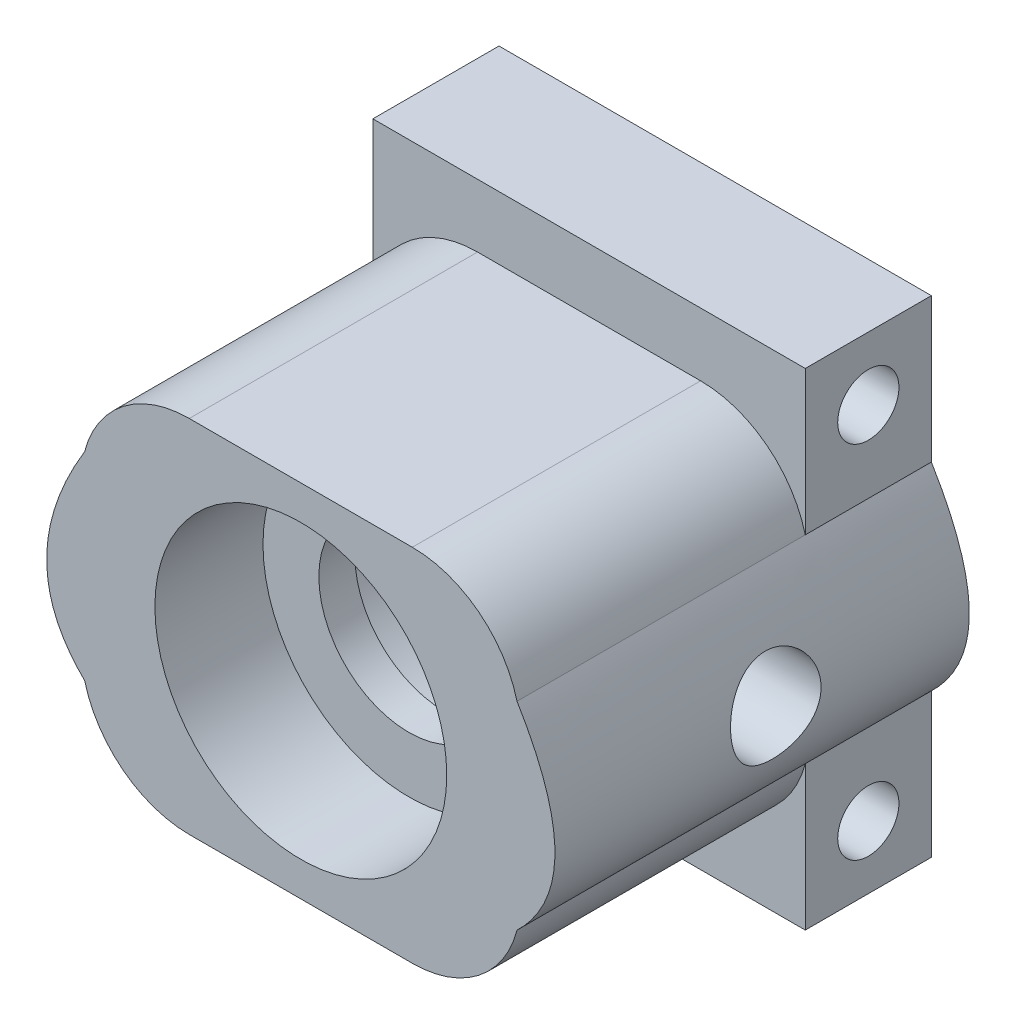
SolidWorks part; units mm, degrees
material "PLA"
ref_plane "Front Plane" through (0, 0, 0) normal (0, 0, 1) x (1, 0, 0)
ref_plane "Top Plane" through (0, 0, 0) normal (0, 1, 0) x (1, 0, 0)
ref_plane "Right Plane" through (0, 0, 0) normal (1, 0, 0) x (0, 0, -1)
sketch "Sketch1" plane through (0, 0, 0) normal (0, 0, 1) x (1, 0, 0)
  line L0 (-12, 13.5) -> (-12, 10)
  line L1 (-12, 10) -> (12, 10)
  line L2 (12, 10) -> (12, 13.5)
  line L3 (12, 13.5) -> (-12, 13.5)
  line L4 (-12, -10) -> (-12, -13.5)
  line L5 (-12, -13.5) -> (12, -13.5)
  line L6 (12, -13.5) -> (12, -10)
  line L7 (12, -10) -> (-12, -10)
  line L8 (0, 10.0333) -> (0, -15.702) construction
  line L9 (-12, 10) -> (-12, -10) construction
  line L10 (12, 10) -> (12, -10) construction
  line L11 (12, 10) -> (12, 5.5)
  line L12 (12, -10) -> (12, -5.5)
  line L13 (10, 10) -> (10, 5.5)
  line L14 (10, -10) -> (10, -5.5)
  line L17 (-10, -10) -> (-10, -5.5)
  line L18 (0, 0) -> (14.9553, 0) construction
  line L19 (-12, -10) -> (-12, -5.5)
  line L20 (-12, 10) -> (-12, 5.5)
  line L21 (-10, 10) -> (-10, 5.5)
  circle A0 centre (0, 0) radius 8.1
  circle A1 centre (0, 0) radius 5
  spline S0 degree 2 poles (12, 5.5) (16.2082, -1.4527) (12, -5.5) knots 0 0 0 0.703674 0.703674 0.703674
  spline S1 degree 2 poles (5.9341, -10) (5.4786, -10.0093) (0, -10) knots 0.968743 0.968743 0.968743 1 1 1
  spline S2 degree 2 poles (10, 5.5) (13.145, -1.5935) (10, -5.5) knots 0 0 0 0.703674 0.703674 0.703674
  spline S3 degree 2 poles (-12, 5.5) (-16.2082, -1.4527) (-12, -5.5) knots 0 0 0 0.703674 0.703674 0.703674
  spline S4 degree 2 poles (-10, 5.5) (-13.145, -1.5935) (-10, -5.5) knots 0 0 0 0.703674 0.703674 0.703674
  point P9 (0, -10)
  point P21 (12, 7.75)
  dimension "D6" = 8
  dimension "D8" = 16.2
  dimension "D9" = 10
  dimension "D5" = 8
  dimension "D1" = 3.5
  dimension "D2" = 3.5
  dimension "D3" = 24
  dimension "D4" = 27
  dimension "D7" = 2
extrude "Boss-Extrude1" add sketch "Sketch1" along normal blind 7 contours L2 L3 L0 L1 | S4 L21 L1 L20 S3 L19 L7 L17 | L13 S2 L14 L7 L12 S0 L11 L1 | L7 S1 L4 L5 L6 | L21 S4 L17 L7 L14 S2 L13 L1 A0 region at (0, 11.75, 0) region at (-11.7448, -0.0184, 0) region at (0, 9.6941, 0) region at (11.7448, -0.0184, 0) region at (-0.0008, -11.7504, 0)
extrude "Boss-Extrude2" add sketch "Sketch1<3>" along normal blind 16 from surface contours L21 S4 L17 L7 L14 S2 L13 L1 A0 | S4 L21 L1 L20 S3 L19 L7 L17 | L13 S2 L14 L7 L12 S0 L11 L1 region at (-11.7448, -0.0184, 0) region at (0, 9.6941, 0) region at (11.7448, -0.0184, 0) starting at face at (4.4506, -10, 7)
sketch "Sketch1<3>" plane through (0, 0, 0) normal (0, 0, 1) x (1, 0, 0) same geometry as "Sketch1"
sketch "Sketch2" plane through (-12, 0, 0) normal (-1, 0, 0) x (0, 0, 1)
  line L0 (7, -13.5) -> (0, -13.5) construction
  line L3 (3.5, 10) -> (3.5, -10) construction
  line L4 (7, -10) -> (7, -13.5) construction
  line L5 (0, -13.5) -> (0, -5.5) construction
  point P0 (3.5, 10)
  point P1 (3.5, -10)
  dimension "D1" = 20
  dimension "D2" = 3.5
hole_wizard "M3 Clearance Hole1" positions "Sketch3" profile "Sketch4" hole size "M3" standard "ISO" end condition through all
sketch "Sketch3" plane through (-12, 0, 0) normal (-1, 0, 0) x (0, 0, 1)
  point P0 (3.5, 10)
  point P3 (3.5, -10)
sketch "Sketch4" plane through (-12, 10, 3.5) normal (0, 1, 0) x (0, 0, 1)
  line L0 (0, 0) -> (0, 26.1041)
  line L1 (0, 26.1041) -> (1.7, 26.1041)
  line L2 (1.7, 26.1041) -> (1.7, 0)
  line L5 (1.7, 0) -> (0, 0)
  line L11 (0, -6.35) -> (0, 107.95) construction
  dimension "Thru Hole Dia." = 3.4
  dimension "Thru Hole Depth" = 26.1041
sketch "Sketch5" plane through (0, 13.5, 0) normal (0, 1, 0) x (1, 0, 0)
  line L0 (12, 0) -> (-12, 0) construction
  point P0 (0, -14)
  dimension "D1" = 14
fillet "Fillet1" radius 6 4 edges at (-12, 10, 15) (12, 10, 15) (12, -10, 15) (-12, -10, 15)
extrude "Boss-Extrude3" add sketch "Sketch1<4>" along normal blind 2 from offset 15 contours A0 A1 region at (-7.8709, 0, 0)
sketch "Sketch1<4>" plane through (0, 0, 0) normal (0, 0, 1) x (1, 0, 0) same geometry as "Sketch1"
fillet "Fillet2" radius 2 1 edges at (8.1, 0, 0)
sketch "Sketch6" plane through (0, 0, 0) normal (1, 0, 0) x (0, 0, -1)
  line L0 (0, -5.5) -> (0, 5.5) construction
  circle A0 centre (-10.7, 0) radius 2.5
  dimension "D1" = 5
  dimension "D2" = 10.7
extrude "Cut-Extrude1" cut sketch "Sketch6" against normal through all both and the other way through all
